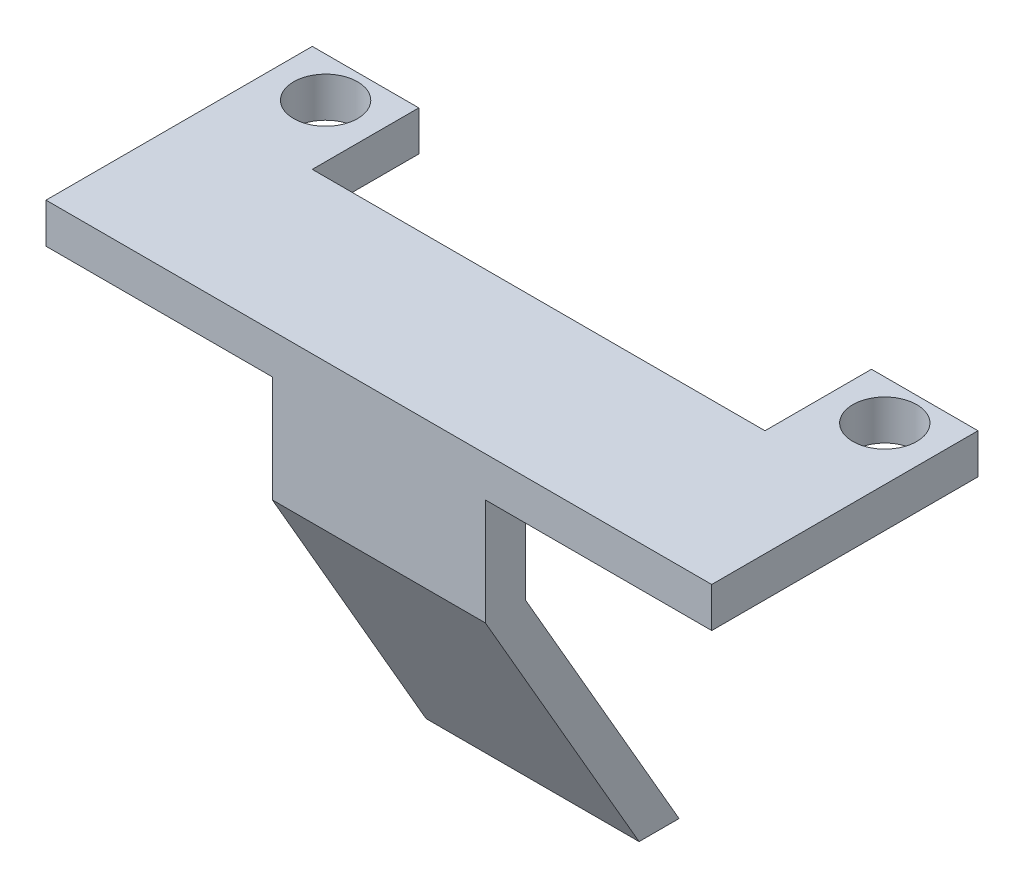
SolidWorks part; units mm, degrees
material "Windform LX 3.0"
ref_plane "Front" through (0, 0, 0) normal (0, 0, 1) x (1, 0, 0)
ref_plane "Top" through (0, 0, 0) normal (0, 1, 0) x (1, 0, 0)
ref_plane "Right" through (0, 0, 0) normal (1, 0, 0) x (0, 0, -1)
sketch "Sketch1" plane through (0, 0, 0) normal (0, 1, 0) x (1, 0, 0)
  line L0 (-8.5, 0) -> (8.5, 0) construction
  line L1 (-8.5, 0) -> (-8.5, -4)
  line L2 (-8.5, -4) -> (8.5, -4)
  line L3 (8.5, -4) -> (8.5, 0)
  line L4 (8.5, 0) -> (12.5, 0)
  line L5 (12.5, 0) -> (12.5, -10)
  line L6 (12.5, -10) -> (-12.5, -10)
  line L7 (-12.5, -10) -> (-12.5, 0)
  line L8 (-12.5, 0) -> (-8.5, 0)
  line L9 (-10.5, 0) -> (-10.5, -1.5) construction
  line L10 (-10.5, -1.5) -> (10.5, -1.5) construction
  line L11 (10.5, -1.5) -> (10.5, 0) construction
  line L12 (-10.5, -1.5) -> (-12.5, -1.5) construction
  circle A0 centre (-10.5, -1.5) radius 1.2
  circle A1 centre (10.5, -1.5) radius 1.2
  point P4 (0, 0)
  dimension "D7" = 2.4
  dimension "D1" = 4
  dimension "D2" = 4
  dimension "D3" = 4
  dimension "D4" = 21
  dimension "D5" = 10
  dimension "D6" = 1.5
extrude "Boss-Extrude1" add sketch "Sketch1" along normal blind 1.5
sketch "Sketch2" plane through (0, 0, 0) normal (0, -1, 0) x (1, 0, 0)
  line L5 (-12.5, 10) -> (12.5, 10) construction
  line L6 (-4, 10) -> (4, 10)
  line L7 (-4, 10) -> (-4, 8.5)
  line L8 (-4, 8.5) -> (4, 8.5)
  line L9 (4, 10) -> (4, 8.5)
  line L10 (0, 0) -> (0, 10) construction
  dimension "D1" = 1.5
  dimension "D2" = 4
extrude "Boss-Extrude2" add sketch "Sketch2" along normal blind 4
sketch "Sketch3" plane through (-4, 0, 0) normal (-1, 0, 0) x (0, 0, 1)
  line L0 (10, -4) -> (4.2265, -14)
  line L1 (4.2265, -14) -> (2.7265, -14)
  line L2 (2.7265, -14) -> (8.5, -4)
  line L3 (8.5, -4) -> (10, -4)
  line L4 (10, -4) -> (10, 0) construction
  dimension "D1" = 1.5
  dimension "D2" = 210
  dimension "D3" = 10
extrude "Boss-Extrude3" add sketch "Sketch3" against normal up to surface (8 mm away) up to face at (4, -2, 9.25)
